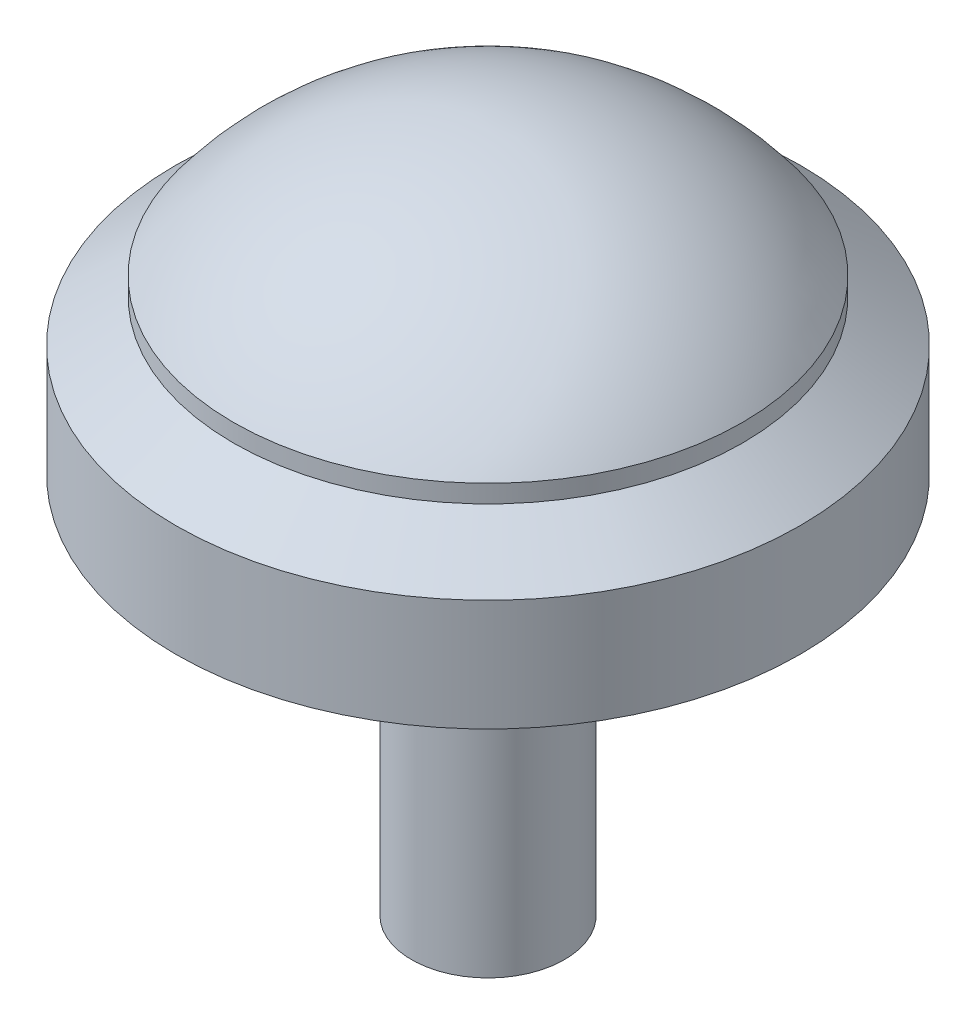
SolidWorks part; units mm, degrees
ref_plane "Front Plane" through (0, 0, 0) normal (0, 0, 1) x (1, 0, 0)
ref_plane "Top Plane" through (0, 0, 0) normal (0, 1, 0) x (1, 0, 0)
ref_plane "Right Plane" through (0, 0, 0) normal (1, 0, 0) x (0, 0, -1)
sketch "Sketch1" plane through (0, 0, 0) normal (0, 1, 0) x (1, 0, 0)
  circle A0 centre (0, 0) radius 49
  dimension "D1" = 98
extrude "Boss-Extrude1" add sketch "Sketch1" along normal blind 25.5 contours A0
sketch "Sketch2" plane through (0, 25.5, 0) normal (0, 1, 0) x (1, 0, 0)
  circle A0 centre (0, 0) radius 39.95
  dimension "D1" = 79.9
extrude "Boss-Extrude2" add sketch "Sketch2" along normal blind 1.5 contours A0
dome "Dome1" faces to dome 1 distance 20 reverse direction no elliptical dome no face at (0, 27, 39.95) parameters "D1"=20
chamfer "Chamfer1" distance 8 angle 53.5 1 edges at (0, 25.5, 49) first distance on face at (0, 25.5, 49)
sketch "Sketch3" plane through (0, 0, 0) normal (0, -1, 0) x (1, 0, 0)
  line L0 (46.8451, -50.3337) -> (46.8451, -44.7932)
  circle A0 centre (0, 0) radius 12
  point P5 (0, 0)
  dimension "D1" = 24
extrude "Boss-Extrude3" add sketch "Sketch3" along normal blind 60 contours A0 | A0 region at (0, 0, 0)
